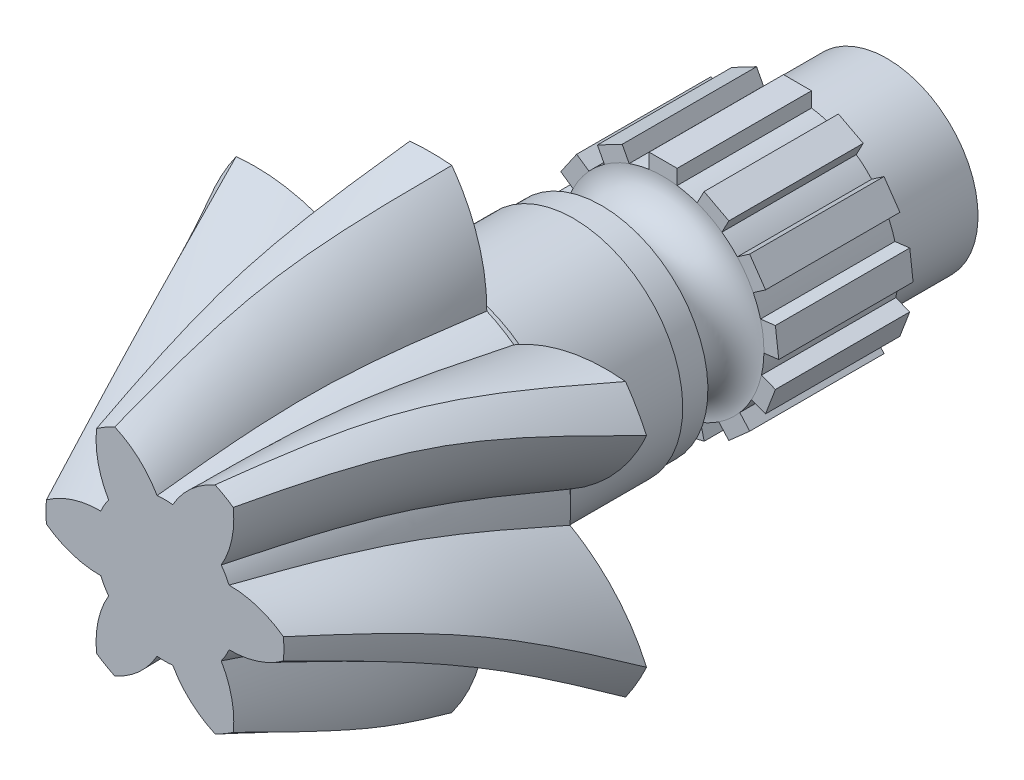
SolidWorks part; units mm, degrees
ref_plane "Ön Düzlem" through (0, 0, 0) normal (0, 0, 1) x (1, 0, 0)
ref_plane "Üst Düzlem" through (0, 0, 0) normal (0, 1, 0) x (1, 0, 0)
ref_plane "Sağ Düzlem" through (0, 0, 0) normal (1, 0, 0) x (0, 0, -1)
sketch "Sketch1" plane through (0, 0, 0) normal (1, 0, 0) x (0, 0, -1)
  line L0 (0, 0) -> (0, 45)
  line L1 (0, 45) -> (5, 45)
  line L2 (5, 45) -> (5, 39)
  line L3 (5, 39) -> (51, 39)
  line L4 (51, 39) -> (51, 38)
  line L5 (51, 38) -> (61, 38)
  line L6 (61, 38) -> (61, 36)
  line L7 (83, 36) -> (131, 36)
  line L8 (131, 36) -> (131, 32.5)
  line L9 (131, 32.5) -> (163, 32.5)
  line L10 (163, 32.5) -> (163, 0)
  line L11 (163, 0) -> (0, 0)
  arc A0 (61, 36) -> (83, 36) centre (72, 36) ccw
  dimension "D1" = 45
  dimension "D2" = 163
  dimension "D3" = 5
  dimension "D4" = 32
  dimension "D5" = 80
  dimension "D6" = 102
  dimension "D7" = 112
  dimension "D8" = 39
  dimension "D9" = 38
  dimension "D10" = 36
  dimension "D11" = 32.5
revolve "Revolve1" add sketch "Sketch1" angle 360 about L11
sketch "Sketch2" plane through (0, 0, 0) normal (0, 0, 1) x (1, 0, 0)
  line L0 (0, 0) -> (0, 85) construction
  arc A0 (7.5, 84.6685) -> (-7.5, 84.6685) centre (0, 0) ccw
  arc A2 (-7.5, 84.6685) -> (-20, 45.8258) centre (44.998, 46.3414) ccw
  arc A3 (7.5, 84.6685) -> (20, 45.8258) centre (-44.998, 46.3414) cw
  arc A4 (69.575, 48.8294) -> (29.6863, 40.2334) centre (62.6318, -15.7987) ccw
  arc A5 (77.075, 35.839) -> (69.575, 48.8294) centre (0, 0) ccw
  arc A6 (77.075, 35.839) -> (49.6863, 5.5924) centre (17.6338, 62.1401) cw
  arc A7 (77.075, -35.839) -> (49.6863, -5.5924) centre (17.6338, -62.1401) ccw
  arc A8 (69.575, -48.8294) -> (77.075, -35.839) centre (0, 0) ccw
  arc A9 (69.575, -48.8294) -> (29.6863, -40.2334) centre (62.6318, 15.7987) cw
  arc A10 (7.5, -84.6685) -> (20, -45.8258) centre (-44.998, -46.3414) ccw
  arc A11 (-7.5, -84.6685) -> (7.5, -84.6685) centre (0, 0) ccw
  arc A12 (-7.5, -84.6685) -> (-20, -45.8258) centre (44.998, -46.3414) cw
  arc A13 (-69.575, -48.8294) -> (-29.6863, -40.2334) centre (-62.6318, 15.7987) ccw
  arc A14 (-77.075, -35.839) -> (-69.575, -48.8294) centre (0, 0) ccw
  arc A15 (-77.075, -35.839) -> (-49.6863, -5.5924) centre (-17.6338, -62.1401) cw
  arc A16 (-77.075, 35.839) -> (-49.6863, 5.5924) centre (-17.6338, 62.1401) ccw
  arc A17 (-69.575, 48.8294) -> (-77.075, 35.839) centre (0, 0) ccw
  arc A18 (-69.575, 48.8294) -> (-29.6863, 40.2334) centre (-62.6318, -15.7987) cw
  arc A26 (-49.6863, 5.5924) -> (-49.6863, -5.5924) centre (0, 0) ccw
  arc A27 (-29.6863, -40.2334) -> (-20, -45.8258) centre (0, 0) ccw
  arc A28 (20, -45.8258) -> (29.6863, -40.2334) centre (0, 0) ccw
  arc A29 (49.6863, -5.5924) -> (49.6863, 5.5924) centre (0, 0) ccw
  arc A30 (29.6863, 40.2334) -> (20, 45.8258) centre (0, 0) ccw
  arc A31 (-20, 45.8258) -> (-29.6863, 40.2334) centre (0, 0) ccw
  point P54 (0, 0)
  dimension "D1" = 170
  dimension "D2" = 50
  dimension "D3" = 15
  dimension "D5" = 65
  dimension "D4" = 40
  dimension "D6" = 6
ref_plane "Plane1" through (0, 0, 45) normal (0, 0, 1) x (1, 0, 0)
sketch "Sketch3" plane through (0, 0, 45) normal (0, 0, 1) x (1, 0, 0)
  line L0 (0, 0) -> (-16.4997, 61.5778) construction
  line L2 (0, 0) -> (0, 85) construction
  arc A24 (-11.002, 62.7935) -> (-21.8687, 59.8817) centre (0, 0) ccw
  arc A25 (-21.8687, 59.8817) -> (-23.3843, 29.3159) centre (23.603, 42.3065) ccw
  arc A26 (-23.3843, 29.3159) -> (-29.3159, 23.3843) centre (0, 0) ccw
  arc A27 (-29.3159, 23.3843) -> (-59.8817, 21.8687) centre (-42.3065, -23.603) ccw
  arc A28 (-59.8817, 21.8687) -> (-62.7935, 11.002) centre (0, 0) ccw
  arc A29 (-62.7935, 11.002) -> (-37.0805, -5.5935) centre (-24.837, 41.594) ccw
  arc A30 (-37.0805, -5.5935) -> (-34.9094, -13.6962) centre (0, 0) ccw
  arc A31 (-34.9094, -13.6962) -> (-48.8797, -40.9248) centre (-0.7125, -48.44) ccw
  arc A32 (-48.8797, -40.9248) -> (-40.9248, -48.8797) centre (0, 0) ccw
  arc A33 (-40.9248, -48.8797) -> (-13.6962, -34.9094) centre (-48.44, -0.7125) ccw
  arc A34 (-13.6962, -34.9094) -> (-5.5935, -37.0805) centre (0, 0) ccw
  arc A35 (-5.5935, -37.0805) -> (11.002, -62.7935) centre (41.594, -24.837) ccw
  arc A36 (11.002, -62.7935) -> (21.8687, -59.8817) centre (0, 0) ccw
  arc A37 (21.8687, -59.8817) -> (23.3843, -29.3159) centre (-23.603, -42.3065) ccw
  arc A38 (23.3843, -29.3159) -> (29.3159, -23.3843) centre (0, 0) ccw
  arc A39 (29.3159, -23.3843) -> (59.8817, -21.8687) centre (42.3065, 23.603) ccw
  arc A40 (59.8817, -21.8687) -> (62.7935, -11.002) centre (0, 0) ccw
  arc A41 (62.7935, -11.002) -> (37.0805, 5.5935) centre (24.837, -41.594) ccw
  arc A42 (37.0805, 5.5935) -> (34.9094, 13.6962) centre (0, 0) ccw
  arc A43 (34.9094, 13.6962) -> (48.8797, 40.9248) centre (0.7125, 48.44) ccw
  arc A44 (48.8797, 40.9248) -> (40.9248, 48.8797) centre (0, 0) ccw
  arc A45 (40.9248, 48.8797) -> (13.6962, 34.9094) centre (48.44, 0.7125) ccw
  arc A46 (13.6962, 34.9094) -> (5.5935, 37.0805) centre (0, 0) ccw
  arc A47 (5.5935, 37.0805) -> (-11.002, 62.7935) centre (-41.594, 24.837) ccw
  dimension "D1" = 15
ref_plane "Plane2" through (0, 0, 95) normal (0, 0, 1) x (1, 0, 0)
sketch "Sketch4" plane through (0, 0, 95) normal (0, 0, 1) x (1, 0, 0)
  arc A24 (-17.9195, 38.5375) -> (-24.4147, 34.7875) centre (0, 0) ccw
  arc A25 (-24.4147, 34.7875) -> (-20.1167, 14.8431) centre (7.8993, 31.3159) ccw
  arc A26 (-20.1167, 14.8431) -> (-22.9129, 10) centre (0, 0) ccw
  arc A27 (-22.9129, 10) -> (-42.3342, 3.75) centre (-23.1707, -22.499) ccw
  arc A28 (-42.3342, 3.75) -> (-42.3342, -3.75) centre (0, 0) ccw
  arc A29 (-42.3342, -3.75) -> (-22.9129, -10) centre (-23.1707, 22.499) ccw
  arc A30 (-22.9129, -10) -> (-20.1167, -14.8431) centre (0, 0) ccw
  arc A31 (-20.1167, -14.8431) -> (-24.4147, -34.7875) centre (7.8993, -31.3159) ccw
  arc A32 (-24.4147, -34.7875) -> (-17.9195, -38.5375) centre (0, 0) ccw
  arc A33 (-17.9195, -38.5375) -> (-2.7962, -24.8431) centre (-31.07, -8.8169) ccw
  arc A34 (-2.7962, -24.8431) -> (2.7962, -24.8431) centre (0, 0) ccw
  arc A35 (2.7962, -24.8431) -> (17.9195, -38.5375) centre (31.07, -8.8169) ccw
  arc A36 (17.9195, -38.5375) -> (24.4147, -34.7875) centre (0, 0) ccw
  arc A37 (24.4147, -34.7875) -> (20.1167, -14.8431) centre (-7.8993, -31.3159) ccw
  arc A38 (20.1167, -14.8431) -> (22.9129, -10) centre (0, 0) ccw
  arc A39 (22.9129, -10) -> (42.3342, -3.75) centre (23.1707, 22.499) ccw
  arc A40 (42.3342, -3.75) -> (42.3342, 3.75) centre (0, 0) ccw
  arc A41 (42.3342, 3.75) -> (22.9129, 10) centre (23.1707, -22.499) ccw
  arc A42 (22.9129, 10) -> (20.1167, 14.8431) centre (0, 0) ccw
  arc A43 (20.1167, 14.8431) -> (24.4147, 34.7875) centre (-7.8993, 31.3159) ccw
  arc A44 (24.4147, 34.7875) -> (17.9195, 38.5375) centre (0, 0) ccw
  arc A45 (17.9195, 38.5375) -> (2.7962, 24.8431) centre (31.07, 8.8169) ccw
  arc A46 (2.7962, 24.8431) -> (-2.7962, 24.8431) centre (0, 0) ccw
  arc A47 (-2.7962, 24.8431) -> (-17.9195, 38.5375) centre (-31.07, 8.8169) ccw
loft "Loft1" add profiles "Sketch2", "Sketch3", "Sketch4" connector at (7.5, 84.6685, 0) connector at (-11.002, 62.7935, 45) connector at (-17.9195, 38.5375, 95)
sketch "Sketch6" plane through (0, 0, -131) normal (0, 0, -1) x (-1, 0, 0)
  line L1 (-5, 41) -> (5, 41)
  line L2 (-5, 41) -> (-5, 35.6511)
  line L3 (-5, 35.6511) -> (5, 35.6511)
  line L4 (5, 41) -> (5, 35.6511)
  line L5 (0, 35.6511) -> (0, 41) construction
  line L6 (-5, 38.3255) -> (5, 38.3255) construction
  circle A0 centre (0, 0) radius 36
  circle A1 centre (0, 0) radius 36 construction
  point P3 (0, 38.3255)
  circle M3 centre (0, 0) radius 36
  dimension "D1" = 72
  dimension "D2" = 10
  dimension "D3" = 41
extrude "Boss-Extrude1" add sketch "Sketch6" against normal blind 48 contours L4 L1 L2 M3 region at (0, 38.4409, -131)
pattern_circular "CirPattern1" count 13 over 360 about axis through (0, 0, -163) along (0, 0, -1) of "Boss-Extrude1" reverse direction yes
